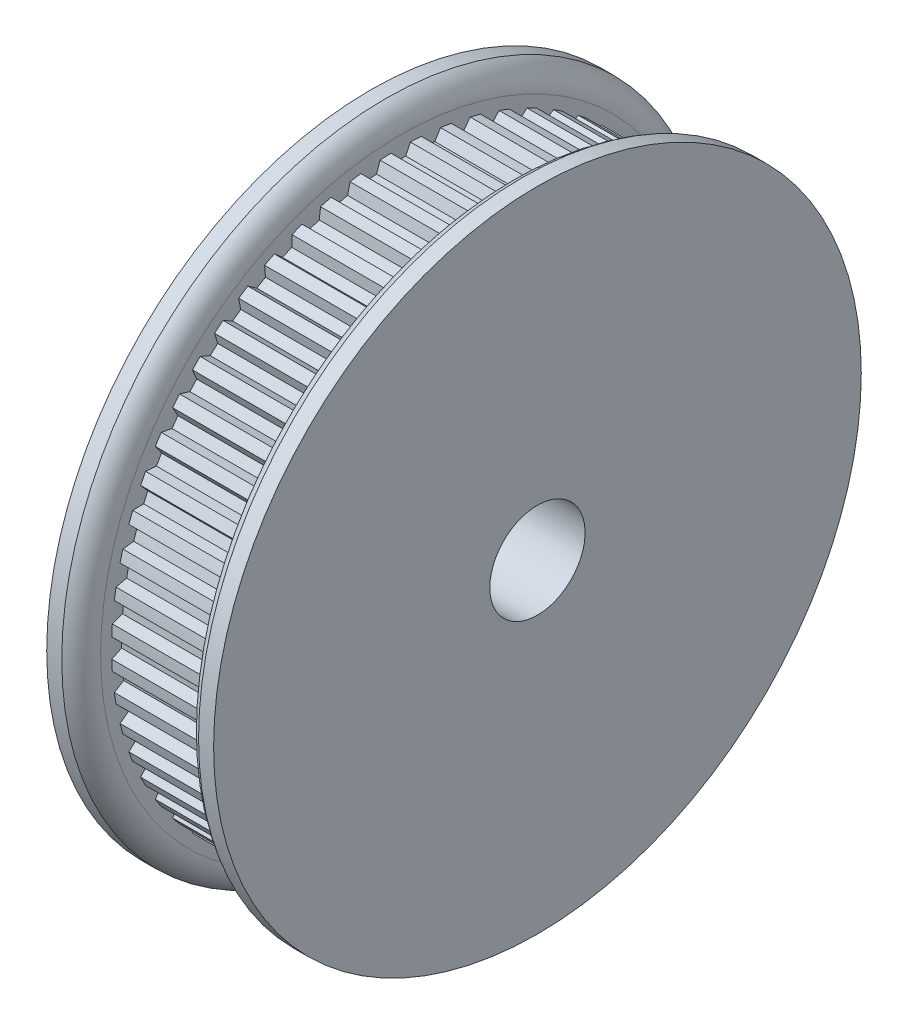
SolidWorks part; units mm, degrees
ref_plane "Front Plane" through (0, 0, 0) normal (0, 0, 1) x (1, 0, 0)
ref_plane "Top Plane" through (0, 0, 0) normal (0, 1, 0) x (1, 0, 0)
ref_plane "Right Plane" through (0, 0, 0) normal (1, 0, 0) x (0, 0, -1)
sketch "Sketch2" plane through (0, 0, 0) normal (1, 0, 0) x (0, 0, -1)
  line L3 (0, 0) -> (0, 18.6055) construction
  line L6 (0, -19.1135) -> (0, -19.431) construction
  line L7 (-0.5715, 19.105) -> (-0.3372, 18.6024)
  line L8 (0.5715, 19.105) -> (0.3372, 18.6024)
  line L9 (-0.5715, 19.105) -> (-0.6445, 19.2615)
  line L10 (0.5715, 19.105) -> (0.6445, 19.2615)
  line L12 (-0.3372, 18.6024) -> (0.3372, 18.6024)
  line L14 (0, 19.1135) -> (0, 19.431) construction
  line L15 (0, 0) -> (0, -1.143) construction
  circle A0 centre (0, 0) radius 19.431 construction
  circle A1 centre (0, 0) radius 18.6055 construction
  circle A2 centre (0, 0) radius 19.1135 construction
  arc A7 (0.6445, 19.2615) -> (-0.6445, 19.2615) centre (0, 0) ccw
  point P5 (0, 19.2722)
  dimension "D3" = 0.3175
  dimension "D1" = 50
sketch "Sketch1" plane through (0, 0, 0) normal (0, 0, 1) x (1, 0, 0)
  line L0 (-8.7376, 0) -> (8.7376, 0) construction
  line L1 (-8.7376, 3.175) -> (8.7376, 3.175)
  line L2 (-8.7376, 3.175) -> (-8.7376, 8.7376)
  line L3 (-2.3876, 21.59) -> (-1.3843, 21.59)
  line L4 (-0.381, 19.431) -> (-0.381, 20.0025)
  line L5 (-0.381, 20.574) -> (-0.381, 19.431) construction
  line L6 (-0.381, 19.431) -> (6.731, 19.431)
  line L7 (6.731, 19.431) -> (6.731, 20.0025)
  line L8 (6.731, 19.431) -> (8.7376, 19.431) construction
  line L9 (7.7343, 21.59) -> (8.7376, 21.59)
  line L10 (8.7376, 21.59) -> (8.7376, 3.175)
  line L11 (7.7343, 19.431) -> (7.7343, 21.59) construction
  line L12 (-5.5626, 8.7376) -> (-5.5626, 3.175) construction
  line L13 (-2.3876, 21.59) -> (-2.3876, 8.7376)
  line L14 (-2.3876, 8.7376) -> (-8.7376, 8.7376)
  arc A0 (6.731, 20.0025) -> (7.7343, 21.59) centre (8.4886, 20.0025) cw
  arc A1 (-0.381, 20.0025) -> (-1.3843, 21.59) centre (-2.1386, 20.0025) ccw
  dimension "Bore Size" = 6.35
  dimension "Overall Width" = 17.4752
  dimension "Inside Width" = 7.112
  dimension "OD" = 43.18
  dimension "D2" = 38.862
  dimension "D3" = 1.143
  dimension "D4" = 0.5715
  dimension "Outside Width" = 11.1252
revolve "Revolve1" add sketch "Sketch1" angle 360 mid plane about L0
sketch "Sketch4" plane through (-0.381, 0, 0) normal (1, 0, 0) x (0, 0, -1)
  circle A0 centre (0, 0) radius 19.2722
  circle A2 centre (0, 0) radius 19.431
  circle A3 centre (0, 0) radius 19.431 construction
extrude "Cut-Extrude2" cut sketch "Sketch4" along normal up to surface (7.112 mm away) up to face at (6.731, 0, 19.431)
sketch "Sketch3" plane through (-0.381, 0, 0) normal (1, 0, 0) x (0, 0, -1)
  line L2 (-0.5715, 19.105) -> (-0.3372, 18.6024) construction
  line L3 (-0.3372, 18.6024) -> (0.3372, 18.6024) construction
  line L4 (0.5715, 19.105) -> (0.3372, 18.6024) construction
  line L5 (-0.6445, 19.2615) -> (-0.3372, 18.6024)
  line L6 (-0.3372, 18.6024) -> (0.3372, 18.6024)
  line L7 (0.6445, 19.2615) -> (0.3372, 18.6024)
  arc A1 (0.6445, 19.2615) -> (-0.6445, 19.2615) centre (0, 0) ccw construction
  arc A2 (0.6445, 19.2615) -> (-0.6445, 19.2615) centre (0, 0) ccw
extrude "Cut-Extrude1" cut sketch "Sketch3" along normal up to surface (7.112 mm away) up to face at (6.731, 0, 20.0025)
pattern_circular "CirPattern1" count 60 over 360 of "Cut-Extrude1"
sketch "Sketch5" plane through (0, 0, 0) normal (0, 0, 1) x (1, 0, 0)
  line L1 (6.731, 20.0025) -> (6.731, -20.0025) construction
  point P0 (6.731, 0)
equation "\"D3@Sketch2\" = (\"hs@Sketch2\"-\"ht@Sketch2\")/2"
equation "\"D2@Sketch1\" = \"PD@Sketch2\""
equation "\"D3@Sketch1\" = \"hs@Sketch2\""
equation "\"D4@Sketch1\" = \"D3@Sketch1\"/2"
